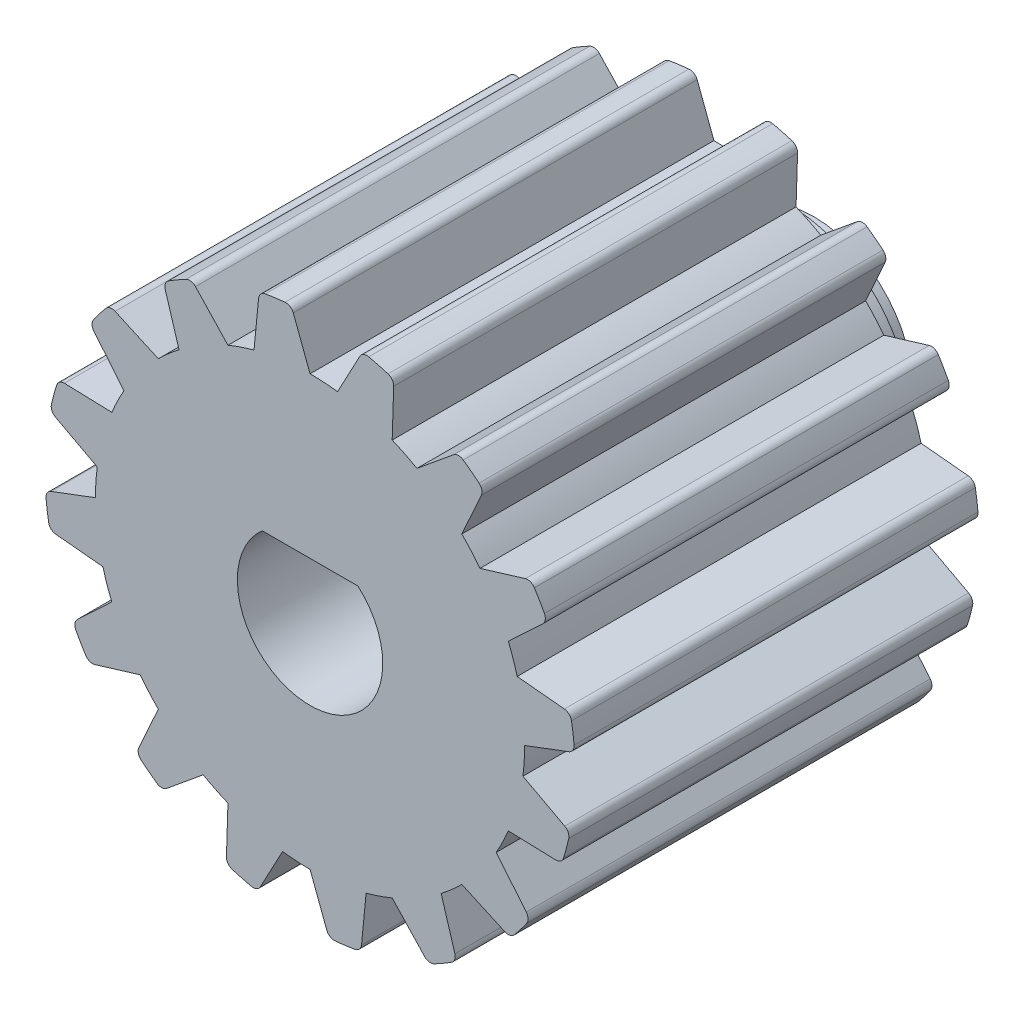
SolidWorks part; units mm, degrees
ref_plane "Alzado" through (0, 0, 0) normal (0, 0, 1) x (1, 0, 0)
ref_plane "Planta" through (0, 0, 0) normal (0, 1, 0) x (1, 0, 0)
ref_plane "Vista lateral" through (0, 0, 0) normal (1, 0, 0) x (0, 0, -1)
sketch "Croquis2" plane through (0, 0, 0) normal (0, 0, 1) x (1, 0, 0)
  line L0 (0, 0) -> (0, 7.9702) construction
  line L2 (-2.0817, 7.6936) -> (-1.9112, 9.4453)
  line L3 (-1.0408, 7.8319) -> (0, 0) construction
  line L4 (0, 7.9702) -> (-0.6221, 9.6166)
  line L5 (1.021, 7.9046) -> (1.8489, 9.4577)
  line L6 (3.0501, 7.3635) -> (3.1053, 9.1227)
  line L7 (3.9682, 6.9122) -> (5.3274, 8.0302)
  line L8 (5.6358, 5.6358) -> (6.3601, 7.2399)
  line L9 (6.3113, 4.8674) -> (7.9949, 5.3803)
  line L10 (7.3635, 3.0501) -> (8.6465, 4.2549)
  line L11 (7.6936, 2.0817) -> (9.4453, 1.9112)
  line L12 (7.9702, 0) -> (9.6166, 0.6221)
  line L13 (7.9046, -1.021) -> (9.4577, -1.8489)
  line L14 (7.3635, -3.0501) -> (9.1227, -3.1053)
  line L15 (6.9122, -3.9682) -> (8.0302, -5.3274)
  line L16 (5.6358, -5.6358) -> (7.2399, -6.3601)
  line L17 (4.8674, -6.3113) -> (5.3803, -7.9949)
  line L18 (3.0501, -7.3635) -> (4.2549, -8.6465)
  line L19 (2.0817, -7.6936) -> (1.9112, -9.4453)
  line L20 (0, -7.9702) -> (0.6221, -9.6166)
  line L21 (-1.021, -7.9046) -> (-1.8489, -9.4577)
  line L22 (-3.0501, -7.3635) -> (-3.1053, -9.1227)
  line L23 (-3.9682, -6.9122) -> (-5.3274, -8.0302)
  line L24 (-5.6358, -5.6358) -> (-6.3601, -7.2399)
  line L25 (-6.3113, -4.8674) -> (-7.9949, -5.3803)
  line L26 (-7.3635, -3.0501) -> (-8.6465, -4.2549)
  line L27 (-7.6936, -2.0817) -> (-9.4453, -1.9112)
  line L28 (-7.9702, 0) -> (-9.6166, -0.6221)
  line L29 (-7.9046, 1.021) -> (-9.4577, 1.8489)
  line L30 (-7.3635, 3.0501) -> (-9.1227, 3.1053)
  line L31 (-6.9122, 3.9682) -> (-8.0302, 5.3274)
  line L32 (-5.6358, 5.6358) -> (-7.2399, 6.3601)
  line L33 (-4.8674, 6.3113) -> (-5.3803, 7.9949)
  line L34 (-3.0501, 7.3635) -> (-4.2549, 8.6465)
  arc A0 (-4.8674, 6.3113) -> (-5.6358, 5.6358) centre (0, 0) ccw
  arc A1 (-7.5914, 6.2764) -> (-8.0413, 5.6886) centre (0, 0) ccw
  arc A2 (-1.6636, 9.7085) -> (-1.9112, 9.4453) centre (-1.6129, 9.4128) ccw
  arc A3 (-0.9298, 9.806) -> (-0.6221, 9.6166) centre (-0.9015, 9.5074) cw
  arc A4 (2.1783, 9.6061) -> (1.8489, 9.4577) centre (2.112, 9.3135) ccw
  arc A5 (2.8935, 9.4154) -> (3.1053, 9.1227) centre (2.8054, 9.1286) cw
  arc A6 (5.6886, 8.0413) -> (5.3274, 8.0302) centre (5.5153, 7.7964) ccw
  arc A7 (6.2764, 7.5914) -> (6.3601, 7.2399) centre (6.0852, 7.3602) cw
  arc A8 (8.3328, 5.2523) -> (7.9949, 5.3803) centre (8.0791, 5.0923) ccw
  arc A9 (8.7037, 4.6117) -> (8.6465, 4.2549) centre (8.4387, 4.4712) cw
  arc A10 (9.7085, 1.6636) -> (9.4453, 1.9112) centre (9.4128, 1.6129) ccw
  arc A11 (9.806, 0.9298) -> (9.6166, 0.6221) centre (9.5074, 0.9015) cw
  arc A12 (9.6061, -2.1783) -> (9.4577, -1.8489) centre (9.3135, -2.112) ccw
  arc A13 (9.4154, -2.8935) -> (9.1227, -3.1053) centre (9.1286, -2.8054) cw
  arc A14 (8.0413, -5.6886) -> (8.0302, -5.3274) centre (7.7964, -5.5153) ccw
  arc A15 (7.5914, -6.2764) -> (7.2399, -6.3601) centre (7.3602, -6.0852) cw
  arc A16 (5.2523, -8.3328) -> (5.3803, -7.9949) centre (5.0923, -8.0791) ccw
  arc A17 (4.6117, -8.7037) -> (4.2549, -8.6465) centre (4.4712, -8.4387) cw
  arc A18 (1.6636, -9.7085) -> (1.9112, -9.4453) centre (1.6129, -9.4128) ccw
  arc A19 (0.9298, -9.806) -> (0.6221, -9.6166) centre (0.9015, -9.5074) cw
  arc A20 (-2.1783, -9.6061) -> (-1.8489, -9.4577) centre (-2.112, -9.3135) ccw
  arc A21 (-2.8935, -9.4154) -> (-3.1053, -9.1227) centre (-2.8054, -9.1286) cw
  arc A22 (-5.6886, -8.0413) -> (-5.3274, -8.0302) centre (-5.5153, -7.7964) ccw
  arc A23 (-6.2764, -7.5914) -> (-6.3601, -7.2399) centre (-6.0852, -7.3602) cw
  arc A24 (-8.3328, -5.2523) -> (-7.9949, -5.3803) centre (-8.0791, -5.0923) ccw
  arc A25 (-8.7037, -4.6117) -> (-8.6465, -4.2549) centre (-8.4387, -4.4712) cw
  arc A26 (-9.7085, -1.6636) -> (-9.4453, -1.9112) centre (-9.4128, -1.6129) ccw
  arc A27 (-9.806, -0.9298) -> (-9.6166, -0.6221) centre (-9.5074, -0.9015) cw
  arc A28 (-9.6061, 2.1783) -> (-9.4577, 1.8489) centre (-9.3135, 2.112) ccw
  arc A29 (-9.4154, 2.8935) -> (-9.1227, 3.1053) centre (-9.1286, 2.8054) cw
  arc A30 (-8.0413, 5.6886) -> (-8.0302, 5.3274) centre (-7.7964, 5.5153) ccw
  arc A31 (-7.5914, 6.2764) -> (-7.2399, 6.3601) centre (-7.3602, 6.0852) cw
  arc A32 (-5.2523, 8.3328) -> (-5.3803, 7.9949) centre (-5.0923, 8.0791) ccw
  arc A33 (-4.6117, 8.7037) -> (-4.2549, 8.6465) centre (-4.4712, 8.4387) cw
  arc A34 (-4.6117, 8.7037) -> (-5.2523, 8.3328) centre (0, 0) ccw
  arc A35 (-0.9298, 9.806) -> (-1.6636, 9.7085) centre (0, 0) ccw
  arc A36 (2.8935, 9.4154) -> (2.1783, 9.6061) centre (0, 0) ccw
  arc A37 (6.2764, 7.5914) -> (5.6886, 8.0413) centre (0, 0) ccw
  arc A38 (8.7037, 4.6117) -> (8.3328, 5.2523) centre (0, 0) ccw
  arc A39 (9.4154, -2.8935) -> (9.6061, -2.1783) centre (0, 0) ccw
  arc A40 (7.5914, -6.2764) -> (8.0413, -5.6886) centre (0, 0) ccw
  arc A41 (-9.4154, 2.8935) -> (-9.6061, 2.1783) centre (0, 0) ccw
  arc A42 (-9.806, -0.9298) -> (-9.7085, -1.6636) centre (0, 0) ccw
  arc A43 (-8.7037, -4.6117) -> (-8.3328, -5.2523) centre (0, 0) ccw
  arc A44 (-6.2764, -7.5914) -> (-5.6886, -8.0413) centre (0, 0) ccw
  arc A45 (-2.8935, -9.4154) -> (-2.1783, -9.6061) centre (0, 0) ccw
  arc A46 (0.9298, -9.806) -> (1.6636, -9.7085) centre (0, 0) ccw
  arc A47 (4.6117, -8.7037) -> (5.2523, -8.3328) centre (0, 0) ccw
  arc A48 (-2.0817, 7.6936) -> (-3.0501, 7.3635) centre (0, 0) ccw
  arc A49 (1.021, 7.9046) -> (0, 7.9702) centre (0, 0) ccw
  arc A50 (3.9682, 6.9122) -> (3.0501, 7.3635) centre (0, 0) ccw
  arc A51 (6.3113, 4.8674) -> (5.6358, 5.6358) centre (0, 0) ccw
  arc A52 (7.6936, 2.0817) -> (7.3635, 3.0501) centre (0, 0) ccw
  arc A53 (7.9046, -1.021) -> (7.9702, 0) centre (0, 0) ccw
  arc A54 (9.806, 0.9298) -> (9.7085, 1.6636) centre (0, 0) ccw
  arc A55 (6.9122, -3.9682) -> (7.3635, -3.0501) centre (0, 0) ccw
  arc A56 (4.8674, -6.3113) -> (5.6358, -5.6358) centre (0, 0) ccw
  arc A57 (2.0817, -7.6936) -> (3.0501, -7.3635) centre (0, 0) ccw
  arc A58 (-1.021, -7.9046) -> (0, -7.9702) centre (0, 0) ccw
  arc A59 (-3.9682, -6.9122) -> (-3.0501, -7.3635) centre (0, 0) ccw
  arc A60 (-6.3113, -4.8674) -> (-5.6358, -5.6358) centre (0, 0) ccw
  arc A61 (-7.6936, -2.0817) -> (-7.3635, -3.0501) centre (0, 0) ccw
  arc A62 (-7.9046, 1.021) -> (-7.9702, 0) centre (0, 0) ccw
  arc A63 (-6.9122, 3.9682) -> (-7.3635, 3.0501) centre (0, 0) ccw
  dimension "D1" = 2.1
  dimension "D2" = 19.7
  dimension "D3" = 15.9404
  dimension "D6" = 0.6
  dimension "D4" = 1.76
extrude "Saliente-Extruir1" add sketch "Croquis2" along normal blind 15
sketch "Croquis3" plane through (0, 0, 15) normal (0, 0, 1) x (1, 0, 0)
  line L0 (0, 0) -> (0, 1.68) construction
  line L1 (-1.4967, 1.68) -> (1.4967, 1.68)
  arc A0 (-1.4967, 1.68) -> (1.4967, 1.68) centre (0, 0) ccw
  point P7 (0, 1.68)
  dimension "D1" = 4.5
  dimension "D2" = 1.68
sketch "Croquis5" plane through (0, 0, 0) normal (0, 0, -1) x (-1, 0, 0)
  circle A0 centre (0, 0) radius 4.5
  dimension "D1" = 9
extrude "Saliente-Extruir2" add sketch "Croquis5" along normal blind 6
extrude "Cortar-Extruir1" cut sketch "Croquis3" against normal through all
scale "Escala1" scale about origin uniform scaling yes scale factor 1.5
sketch "Croquis6" plane through (0, 0, 22.5) normal (0, 0, 1) x (1, 0, 0)
  line L0 (0, -4.05) -> (0, 3.05) construction
  line L1 (2.6646, 3.05) -> (-2.6646, 3.05)
  arc A0 (-2.245, 2.52) -> (2.245, 2.52) centre (0, 0) ccw construction
  arc A1 (-2.245, 2.52) -> (2.245, 2.52) centre (0, 0) ccw construction
  arc A2 (-2.6646, 3.05) -> (2.6646, 3.05) centre (0, 0) ccw
  dimension "D1" = 8.1
  dimension "D2" = 7.1
extrude "Cortar-Extruir2" cut sketch "Croquis6" against normal through all both and the other way through all
sketch "Croquis7" plane through (0, 0, -9) normal (0, 0, -1) x (-1, 0, 0)
  circle A0 centre (0, 0) radius 10
  dimension "D1" = 20
extrude "Cortar-Extruir3" cut sketch "Croquis7" against normal blind 5.8 and the other way through all
sketch "Croquis8" plane through (0, 0, -3.2) normal (0, 0, -1) x (-1, 0, 0)
  line L0 (-2.6646, 3.05) -> (2.6646, 3.05) construction
  line L1 (-2.6646, 3.05) -> (2.6646, 3.05)
  arc A1 (-2.6646, 3.05) -> (2.6646, 3.05) centre (0, 0) ccw construction
  arc A2 (-2.6646, 3.05) -> (2.6646, 3.05) centre (0, 0) ccw
  circle A3 centre (0, 0) radius 5.5
  dimension "D1" = 11
extrude "Saliente-Extruir3" add sketch "Croquis8" along normal blind 2.37
sketch "Croquis9" plane through (0, 0, -3.2) normal (0, 0, -1) x (-1, 0, 0)
  circle A0 centre (0, 0) radius 5.5 construction
  circle A1 centre (0, 0) radius 6.75
  circle A2 centre (0, 0) radius 6.75
  circle A3 centre (0, 0) radius 5.5
  dimension "D1" = 0
extrude "Saliente-Extruir4" add sketch "Croquis9" along normal blind 1
